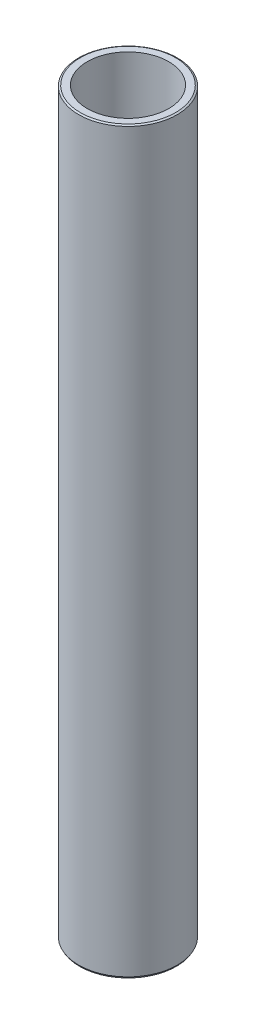
SolidWorks part; units mm, degrees
ref_plane "Front Plane" through (0, 0, 0) normal (0, 0, 1) x (1, 0, 0)
ref_plane "Top Plane" through (0, 0, 0) normal (0, 1, 0) x (1, 0, 0)
ref_plane "Right Plane" through (0, 0, 0) normal (1, 0, 0) x (0, 0, -1)
sketch "Sketch1" plane through (0, 0, 0) normal (0, 1, 0) x (1, 0, 0)
  circle A0 centre (0, 0) radius 40
  dimension "SHAFT_OD" = 80
extrude "Boss-Extrude1" add sketch "Sketch1" along normal blind 600
sketch "Sketch2" plane through (0, 0, 0) normal (0, 1, 0) x (1, 0, 0)
  circle A0 centre (0, 0) radius 33.0727
  dimension "BORE_D" = 66.1453
extrude "Cut-Extrude1" cut sketch "Sketch2" along normal through all
chamfer "Chamfer1" distance 0.7763 angle 60 2 edges at (0, 600, 40) (0, 0, 40) first distance on face at (0, 600, 40) first distance on face at (0, 0, 33.0727)
